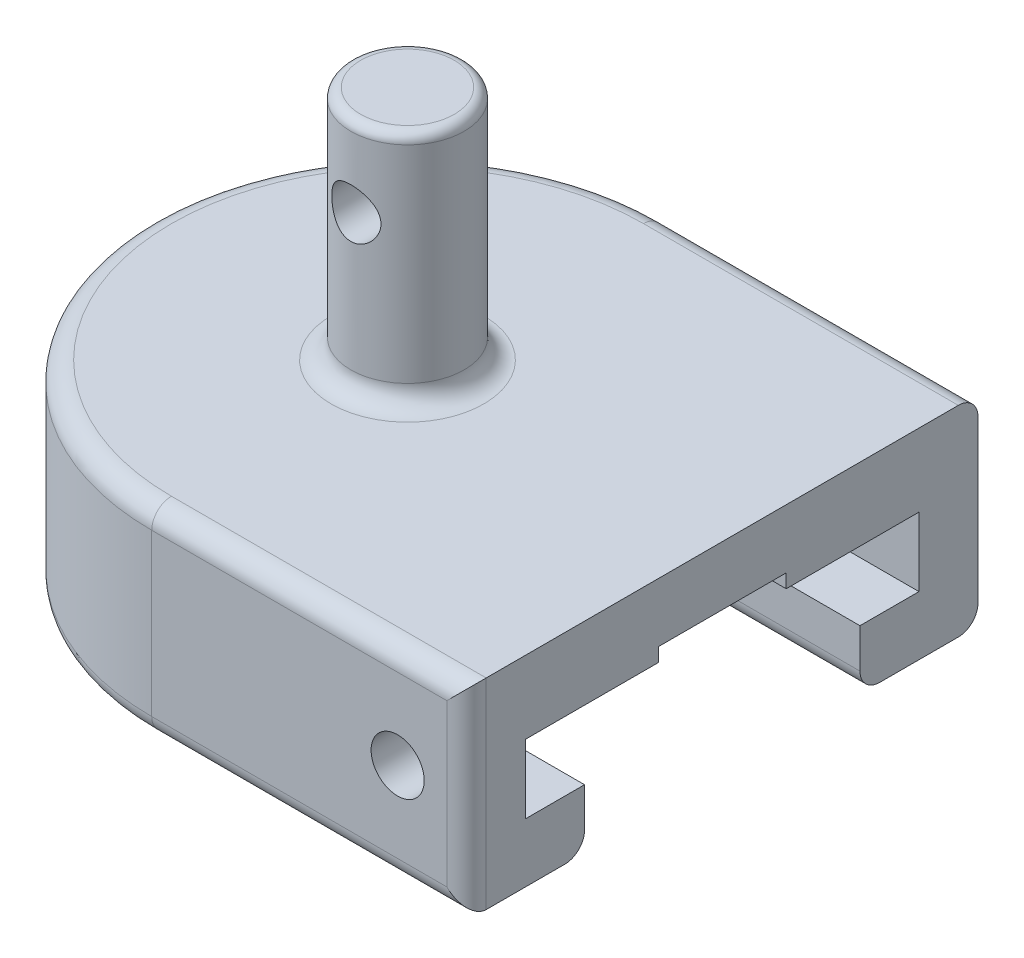
SolidWorks part; units mm, degrees
ref_plane "Front Plane" through (0, 0, 0) normal (0, 0, 1) x (1, 0, 0)
ref_plane "Top Plane" through (0, 0, 0) normal (0, 1, 0) x (1, 0, 0)
ref_plane "Right Plane" through (0, 0, 0) normal (1, 0, 0) x (0, 0, -1)
sketch "Sketch1" plane through (0, 0, 0) normal (0, 1, 0) x (1, 0, 0)
  line L0 (0, 13) -> (16, 13)
  line L1 (0, -13) -> (16, -13)
  line L2 (0, 7) -> (16, 7)
  line L3 (16, 13) -> (16, 7)
  line L4 (0, -7) -> (16, -7)
  line L5 (16, -7) -> (16, -13)
  arc A0 (0, 7) -> (0, -7) centre (0, 0) ccw
  arc A1 (0, 13) -> (0, -13) centre (0, 0) ccw
  dimension "D1" = 6
  dimension "D2" = 7
  dimension "D3" = 16
  dimension "D4" = 16
extrude "Boss-Extrude1" add sketch "Sketch1" along normal blind 3
sketch "Sketch2" plane through (0, 3, 0) normal (0, 1, 0) x (1, 0, 0)
  line L0 (0, 13) -> (16, 13)
  line L1 (16, 13) -> (16, 10)
  line L2 (16, 7) -> (16, 13) construction
  line L3 (16, -13) -> (0, -13)
  line L4 (16, -13) -> (16, -10)
  line L7 (16, -13) -> (16, -7) construction
  line L8 (0, 10) -> (16, 10)
  line L9 (0, -10) -> (16, -10)
  arc A0 (0, 10) -> (0, -10) centre (0, 0) ccw
  arc A1 (0, 13) -> (0, -13) centre (0, 0) ccw
  dimension "D2" = 3
extrude "Boss-Extrude2" add sketch "Sketch2" along normal blind 3.5
sketch "Sketch3" plane through (0, 6.5, 0) normal (0, 1, 0) x (1, 0, 0)
  line L0 (16, 13) -> (0, 13)
  line L1 (16, 13) -> (16, 7)
  line L3 (0, -13) -> (16, -13)
  line L4 (16, -13) -> (16, -7)
  line L5 (16, -7) -> (0, -7) construction
  line L6 (16, -10) -> (16, -7) construction
  line L8 (16, 7) -> (16, -7)
  arc A1 (0, 13) -> (0, -13) centre (0, 0) ccw
extrude "Boss-Extrude3" add sketch "Sketch3" along normal blind 3.7
sketch "Sketch4" plane through (0, 10.2, 0) normal (0, 1, 0) x (1, 0, 0)
  circle A0 centre (0, 0) radius 2.88
  dimension "D1" = 5.76
extrude "Boss-Extrude4" add sketch "Sketch4" along normal blind 12
sketch "Sketch9" plane through (16, 0, 0) normal (1, 0, 0) x (0, 0, -1)
  line L0 (-10, 6.5) -> (10, 6.5) construction
  line L1 (-3.25, 6.5) -> (3.25, 6.5)
  line L2 (-3.25, 6.5) -> (-3.25, 7.2)
  line L3 (-3.25, 7.2) -> (3.25, 7.2)
  line L4 (3.25, 6.5) -> (3.25, 7.2)
  line L5 (0, 10.2) -> (0, 6.5) construction
  line L6 (-13, 10.2) -> (13, 10.2) construction
  line L7 (-10, 6.5) -> (10, 6.5) construction
  line L8 (0, 7.2) -> (0, 6.5) construction
  dimension "D1" = 6.5
  dimension "D2" = 0.7
extrude "Cut-Extrude2" cut sketch "Sketch9" against normal blind 23
hole_wizard "Ø2.5mm Dowel Hole1" positions "3DSketch4" profile "Sketch7" hole size "Ø2.5" standard "ANSI Metric" end condition through all
sketch3d "3DSketch4"
  point P0 (-0.0024, 18.1049, 2.88)
  point P12 (-0.0024, 18.1049, 2.88)
sketch "Sketch7" plane through (-0.0024, 18.1049, 2.88) normal (0, 1, 0) x (1, 0, 0.0008)
  line L0 (0, 0) -> (0, 15.8935)
  line L1 (0, 15.8935) -> (1.25, 15.8935)
  line L2 (1.25, 15.8935) -> (1.25, 0)
  line L5 (1.25, 0) -> (0, 0)
  line L11 (0, -6.35) -> (0, 107.95) construction
  dimension "Thru Hole Dia." = 2.5
  dimension "Thru Hole Depth" = 15.8935
sketch "Sketch8" plane through (0, 0, 13) normal (0, 0, 1) x (1, 0, 0)
  line L0 (16, 5.1) -> (0, 5.1) construction
  line L1 (16, 10.2) -> (16, 0) construction
  line L2 (0, 10.2) -> (0, 0) construction
  circle A0 centre (12.5, 5.1) radius 1.35
  dimension "D1" = 2.7
  dimension "D2" = 3.5
extrude "Cut-Extrude1" cut sketch "Sketch8" against normal through all
fillet "Fillet1" radius 1 10 edges at (8, 10.2, -13) (-13, 10.2, 0) (8, 0, -13) (-13, 0, 0) (8, 10.2, 13) (16, 5.1, 13) (8, 0, 13) (8, 0, -7) (-7, 0, 0) (8, 0, 7)
fillet "Fillet2" radius 1 1 edges at (0, 10.2, 2.88)
fillet "Fillet3" radius 0.5 1 edges at (0, 22.2, 2.88)
